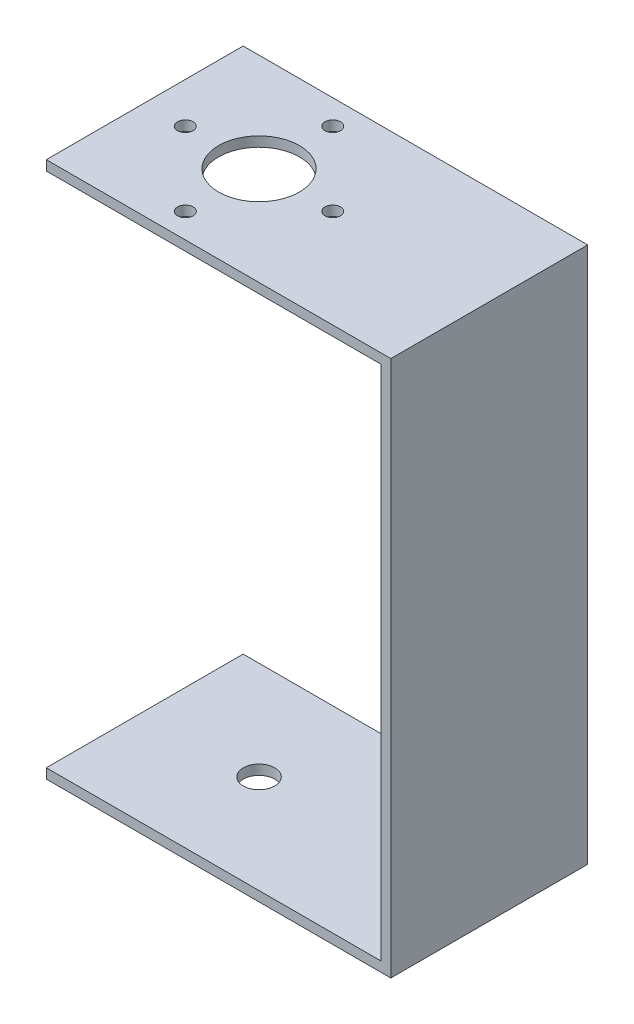
SolidWorks part; units mm, degrees
ref_plane "正面" through (0, 0, 0) normal (0, 0, 1) x (1, 0, 0)
ref_plane "平面" through (0, 0, 0) normal (0, 1, 0) x (1, 0, 0)
ref_plane "右側面" through (0, 0, 0) normal (1, 0, 0) x (0, 0, -1)
sketch "ｽｹｯﾁ1" plane through (0, 0, 0) normal (1, 0, 0) x (0, 0, -1)
  line L1 (0, 0) -> (20, 0)
  line L2 (0, 0) -> (0, 54.5)
  line L3 (0, 54.5) -> (20, 54.5)
  line L4 (20, 0) -> (20, 54.5)
extrude "ﾎﾞｽ - 押し出し1" add sketch "ｽｹｯﾁ1" along normal blind 1
sketch "ｽｹｯﾁ2" plane through (0, 0, 0) normal (-1, 0, 0) x (0, 0, 1)
  line L0 (0, 54.5) -> (0, 0) construction
  line L1 (-20, 54.5) -> (0, 54.5)
  line L2 (-20, 54.5) -> (-20, 53.5)
  line L3 (-20, 53.5) -> (0, 53.5)
  line L4 (0, 54.5) -> (0, 53.5)
extrude "ﾎﾞｽ - 押し出し2" add sketch "ｽｹｯﾁ2" along normal blind 34
sketch "ｽｹｯﾁ3" plane through (0, 0, 0) normal (-1, 0, 0) x (0, 0, 1)
  line L0 (-20, 0) -> (-20, 53.5) construction
  line L1 (0, 0) -> (-20, 0)
  line L2 (0, 0) -> (0, 1)
  line L3 (0, 1) -> (-20, 1)
  line L4 (-20, 0) -> (-20, 1)
extrude "ﾎﾞｽ - 押し出し3" add sketch "ｽｹｯﾁ3" along normal blind 34
sketch "ｽｹｯﾁ4" plane through (0, 54.5, 0) normal (0, 1, 0) x (1, 0, 0)
  circle A0 centre (-22.39, 10) radius 4.1
extrude "ｶｯﾄ - 押し出し1" cut sketch "ｽｹｯﾁ4" against normal blind 1
sketch "ｽｹｯﾁ5" plane through (0, 54.5, 0) normal (0, 1, 0) x (1, 0, 0)
  circle A0 centre (-29.88, 10) radius 0.79
extrude "ｶｯﾄ - 押し出し2" cut sketch "ｽｹｯﾁ5" against normal blind 1
sketch "ｽｹｯﾁ6" plane through (0, 54.5, 0) normal (0, 1, 0) x (1, 0, 0)
  circle A0 centre (-14.9, 10) radius 0.79
extrude "ｶｯﾄ - 押し出し3" cut sketch "ｽｹｯﾁ6" against normal blind 1
sketch "ｽｹｯﾁ7" plane through (0, 54.5, 0) normal (0, 1, 0) x (1, 0, 0)
  circle A0 centre (-22.39, 2.51) radius 0.79
extrude "ｶｯﾄ - 押し出し4" cut sketch "ｽｹｯﾁ7" against normal blind 1
sketch "ｽｹｯﾁ8" plane through (0, 54.5, 0) normal (0, 1, 0) x (1, 0, 0)
  circle A0 centre (-22.39, 17.49) radius 0.79
extrude "ｶｯﾄ - 押し出し5" cut sketch "ｽｹｯﾁ8" against normal blind 1
sketch "ｽｹｯﾁ9" plane through (0, 0, 0) normal (0, -1, 0) x (-1, 0, 0)
  circle A0 centre (22.39, 10) radius 1.6
extrude "ｶｯﾄ - 押し出し6" cut sketch "ｽｹｯﾁ9" against normal blind 1
